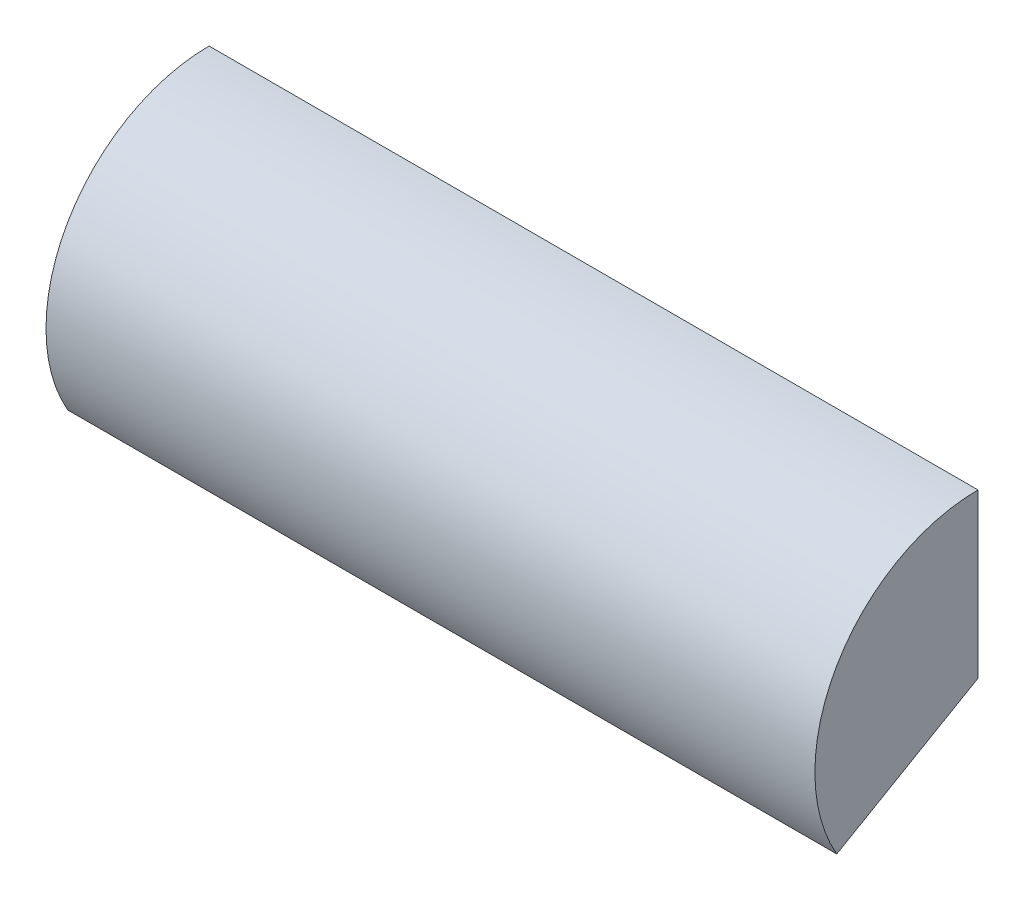
SolidWorks part; units mm, degrees
material "Expanded Polystyrene (EPS)"
ref_plane "Front Plane" through (0, 0, 0) normal (1, 0, 0) x (0, 1, 0)
ref_plane "Top Plane" through (0, 0, 0) normal (0, 0, 1) x (0, 1, 0)
ref_plane "Right Plane" through (0, 0, 0) normal (0, 1, 0) x (-1, 0, 0)
sketch "Sketch1" plane through (0, 0, 0) normal (0, 0, 1) x (0, 1, 0)
  line L1 (0, 0) -> (44.45, 0)
  line L2 (0, 0) -> (0, 215.9)
  line L3 (0, 215.9) -> (44.45, 215.9)
  line L4 (44.45, 0) -> (44.45, 215.9)
  dimension "D1" = 215.9
  dimension "D2" = 44.45
revolve "Revolve1" add sketch "Sketch1" angle 120 about L2 reverse direction yes
sketch "Sketch21" plane through (0, 0, 0) normal (0, 0, -1) x (-1, 0, 0)
  line L1 (215.9, 0) -> (0, 0) construction
  line L2 (71.8627, 22.5006) -> (63.8098, 22.5005) construction
  line L3 (193.3616, 1.4899) -> (73.3627, 22.4963) construction
  line L4 (215.9, 0) -> (0, 0)
  line L5 (71.8627, 22.5006) -> (63.8098, 22.5005)
  line L6 (193.3616, 1.4899) -> (73.3627, 22.4963)
  line L7 (193.3616, 1.4899) -> (193.3615, -0.0101)
  line L8 (71.8627, 22.5006) -> (73.3627, 22.4963)
  line L9 (3.81, 0) -> (3.4091, 11.4291) construction
  line L10 (3.4091, 11.4291) -> (63.8098, 22.5005) construction
  spline S0 degree 2 poles (3.81, 0) (3.4091, 11.4291) (63.8098, 22.5005) knots 0 0 0 1 1 1
  point P9 (3.4091, 11.4291)
revolve "Cut-Revolve21" cut sketch "Sketch21" angle 360 about L4 region at (-84.9213, 8.1739, 0)
sketch "Sketch22" plane through (-215.9, 0, 0) normal (-1, 0, 0) x (0, -1, 0)
  line L2 (-44.45, 0) -> (0, 0)
  line L3 (0, 0) -> (22.225, 38.4948)
  line L4 (-44.45, 0) -> (0, 0)
  line L5 (0, 0) -> (22.225, 38.4948)
  arc A1 (22.225, 38.4948) -> (-44.45, 0) centre (0, 0) ccw
  arc A2 (22.225, 38.4948) -> (-44.45, 0) centre (0, 0) ccw
  dimension "D1" = 0
extrude "Cut-Extrude1" cut sketch "Sketch22" against normal blind 3.175
sketch "Sketch23" plane through (0, 0, 0) normal (1, 0, 0) x (0, 1, 0)
  line L2 (-22.225, 38.4948) -> (0, 0)
  line L3 (0, 0) -> (44.45, 0)
  line L4 (-22.225, 38.4948) -> (0, 0)
  line L5 (0, 0) -> (44.45, 0)
  arc A1 (44.45, 0) -> (-22.225, 38.4948) centre (0, 0) ccw
  arc A2 (44.45, 0) -> (-22.225, 38.4948) centre (0, 0) ccw
  dimension "D1" = 0
extrude "Cut-Extrude2" cut sketch "Sketch23" against normal blind 3.175
